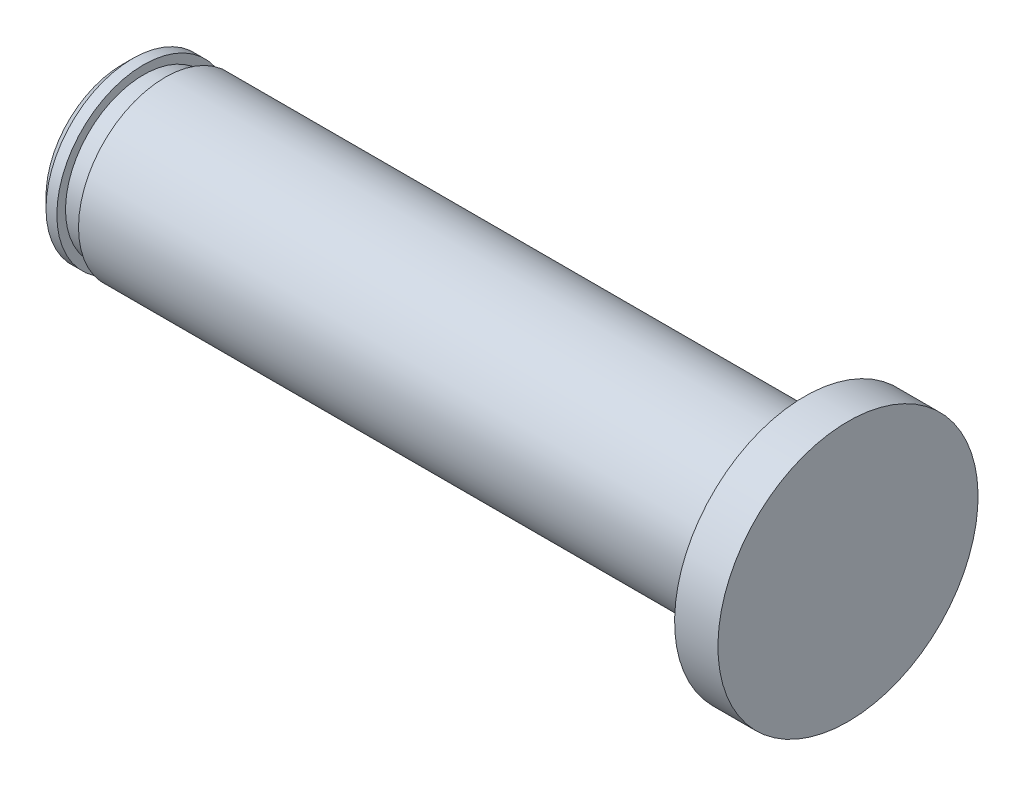
SolidWorks part; units mm, degrees
ref_plane "Спереди" through (0, 0, 0) normal (0, 0, 1) x (1, 0, 0)
ref_plane "Сверху" through (0, 0, 0) normal (0, 1, 0) x (1, 0, 0)
ref_plane "Справа" through (0, 0, 0) normal (1, 0, 0) x (0, 0, -1)
sketch "Эскиз1" plane through (0, 0, 0) normal (0, 0, 1) x (1, 0, 0)
  line L0 (0, 0) -> (-33.5, 0)
  line L1 (-33.5, 0) -> (-33.5, 4)
  line L2 (-33.5, 4) -> (-32.5, 4)
  line L3 (-32.5, 4) -> (-32.5, 3.6)
  line L4 (-32.5, 3.6) -> (-31.5, 3.6)
  line L5 (-31.5, 3.6) -> (-31.5, 4)
  line L6 (-31.5, 4) -> (-2, 4)
  line L7 (-2, 4) -> (-2, 6)
  line L8 (-2, 6) -> (0, 6)
  line L9 (0, 6) -> (0, 0)
  line L10 (-33.5, 0) -> (-24.8571, 0) construction
  line L11 (-32, 0) -> (-50032, 0) construction
  line L12 (-31.5, 4) -> (-31.5, -4) construction
  dimension "D1" = 8
  dimension "D3" = 2
  dimension "D4" = 2
  dimension "D5" = 1
  dimension "D6" = 1
  dimension "D7" = 7.2
revolve "Повернуть1" add sketch "Эскиз1" angle 360 about L10
chamfer "Фаска1" distance 0.5 angle 45 1 edges at (-33.5, -4, 0)
equation "\"Диаметр вала\" = 8  '!!!"
equation "\"Длина вала\" = 28"
equation "\"D1@Эскиз1\"=\"Диаметр вала\""
